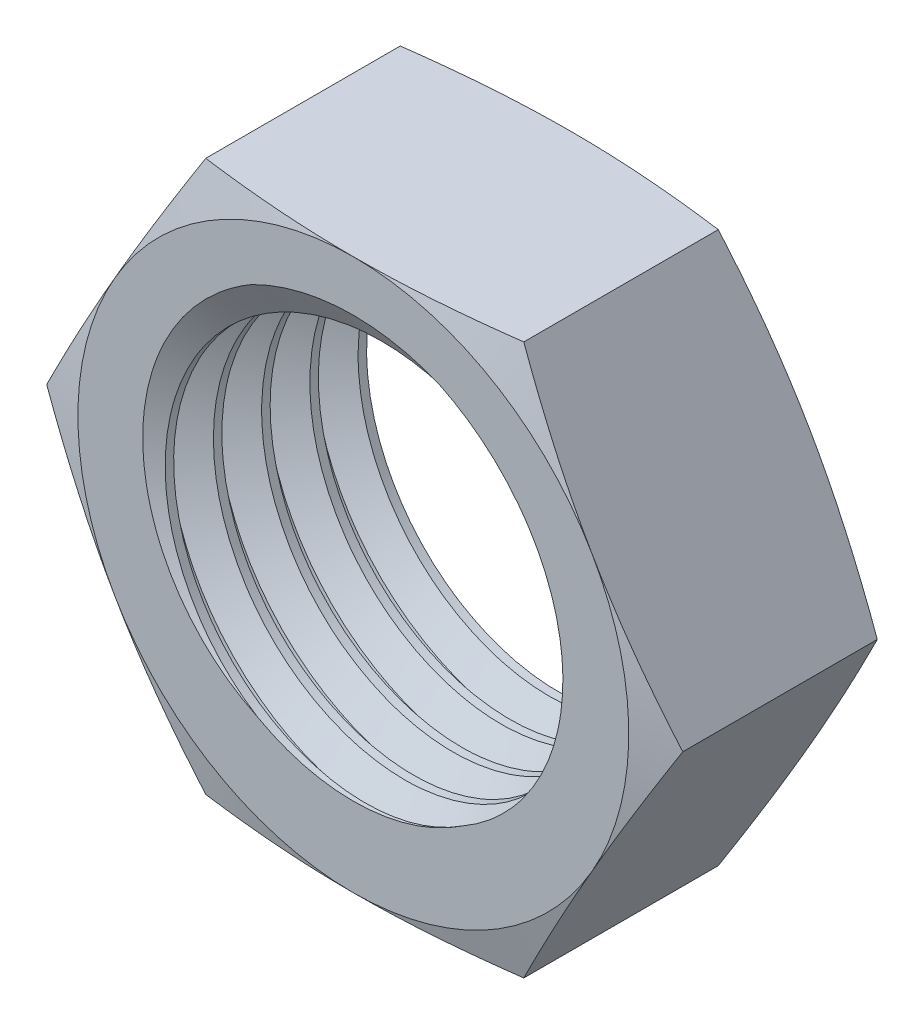
SolidWorks part; units mm, degrees
ref_plane "Płaszczyzna przednia" through (0, 0, 0) normal (0, 0, 1) x (1, 0, 0)
ref_plane "Płaszczyzna górna" through (0, 0, 0) normal (0, 1, 0) x (1, 0, 0)
ref_plane "Płaszczyzna prawa" through (0, 0, 0) normal (1, 0, 0) x (0, 0, -1)
sketch "Szkic1" plane through (0, 0, 0) normal (0, 0, 1) x (1, 0, 0)
  line L1 (6, 10.3923) -> (-6, 10.3923)
  line L2 (-6, 10.3923) -> (-12, 0)
  line L3 (-12, 0) -> (-6, -10.3923)
  line L4 (-6, -10.3923) -> (6, -10.3923)
  line L5 (6, -10.3923) -> (12, 0)
  line L6 (12, 0) -> (6, 10.3923)
  circle A0 centre (0, 0) radius 10.3923 construction
  dimension "D1" = 12
  dimension "D2" = 20.7846
extrude "body" add sketch "Szkic1" along normal blind 8.2 contours L4 L5 L6 L1 L2 L3
sketch "Szkic2" plane through (0, 0, 0) normal (0, 0, 1) x (1, 0, 0)
  circle A0 centre (0, 0) radius 7.4
  dimension "D1" = 14.8
extrude "hole" cut sketch "Szkic2" along normal blind 8.2 contours A0
sketch "Szkic3" plane through (0, 0, 0) normal (0, 0, 1) x (1, 0, 0)
  line L0 (-12, 0) -> (-6, -10.3923) construction
  circle A0 centre (0, 0) radius 10.3923
sketch "Szkic4" plane through (0, 0, 8.2) normal (0, 0, 1) x (1, 0, 0)
  line L0 (6, 10.3923) -> (-6, 10.3923) construction
  circle A0 centre (0, 0) radius 10.3923
extrude "chamfering-top" cut sketch "Szkic4" against normal blind 0.6 draft 75 flip side to cut
extrude "chamfering-bot" cut sketch "Szkic3" along normal blind 0.6 draft 75 flip side to cut contours A0
thread "thread" pitch 2 method cut profile "Profil gwintu1" start angle 23, offset 2, length 12, pitch 1.82, diameter 14.8
ref_plane "Płaszczyzna1" through (6.8117, 2.8914, -2) normal (0.3907, -0.9205, 0) x (0.9205, 0.3907, 0)
sketch "Profil gwintu1" plane through (6.8117, 2.8914, -2) normal (0.3907, -0.9205, 0) x (0.9205, 0.3907, 0)
  line L0 (0, 0) -> (0, 2) construction
  line L1 (0, 0) -> (1.0825, 0.625)
  line L2 (1.0825, 0.625) -> (1.0825, 0.875)
  line L3 (1.0825, 0.875) -> (0, 1.5)
  line L4 (1.0825, 0.75) -> (0, 0.75) construction
  line L11 (0, 0) -> (0, 1.5)
  point P2 (0, 0)
  dimension "Pitch" = 2
  dimension "Profile_Angle" = 60
  dimension "Profile_Land" = 0.25
  dimension "Profile_Height" = 1.0825
